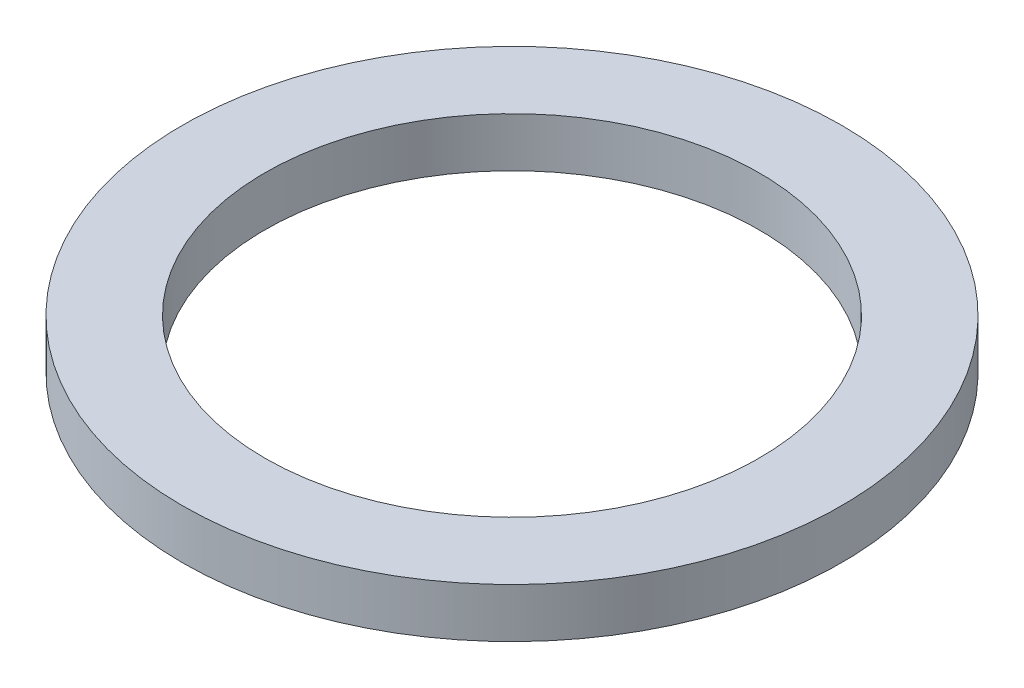
SolidWorks part; units mm, degrees
ref_plane "Front Plane" through (0, 0, 0) normal (0, 0, 1) x (1, 0, 0)
ref_plane "Top Plane" through (0, 0, 0) normal (0, 1, 0) x (1, 0, 0)
ref_plane "Right Plane" through (0, 0, 0) normal (1, 0, 0) x (0, 0, -1)
sketch "Sketch1" plane through (0, 0, 0) normal (0, 1, 0) x (1, 0, 0)
  circle A0 centre (0, 0) radius 60
  dimension "FLANGE_OD" = 120
extrude "Boss-Extrude1" add sketch "Sketch1" along normal blind 9
sketch "Sketch2" plane through (0, 0, 0) normal (0, 1, 0) x (1, 0, 0)
  circle A0 centre (0, 0) radius 45
  dimension "BORE_D" = 90
extrude "Cut-Extrude1" cut sketch "Sketch2" along normal through all
sketch "Sketch3" plane through (0, 9, 0) normal (0, 1, 0) x (1, 0, 0)
  circle A0 centre (0, 0) radius 27.0005 construction
  circle A1 centre (-27.0005, 0) radius 2.3702
  dimension "BOLT_D" = 4.7403
  dimension "BOLT_PCD" = 54.001
extrude "Cut-Extrude2" cut sketch "Sketch3" against normal blind 7.1748 rebuild error yes
pattern_circular "CirPattern1" count 6 over 360 rebuild error yes
